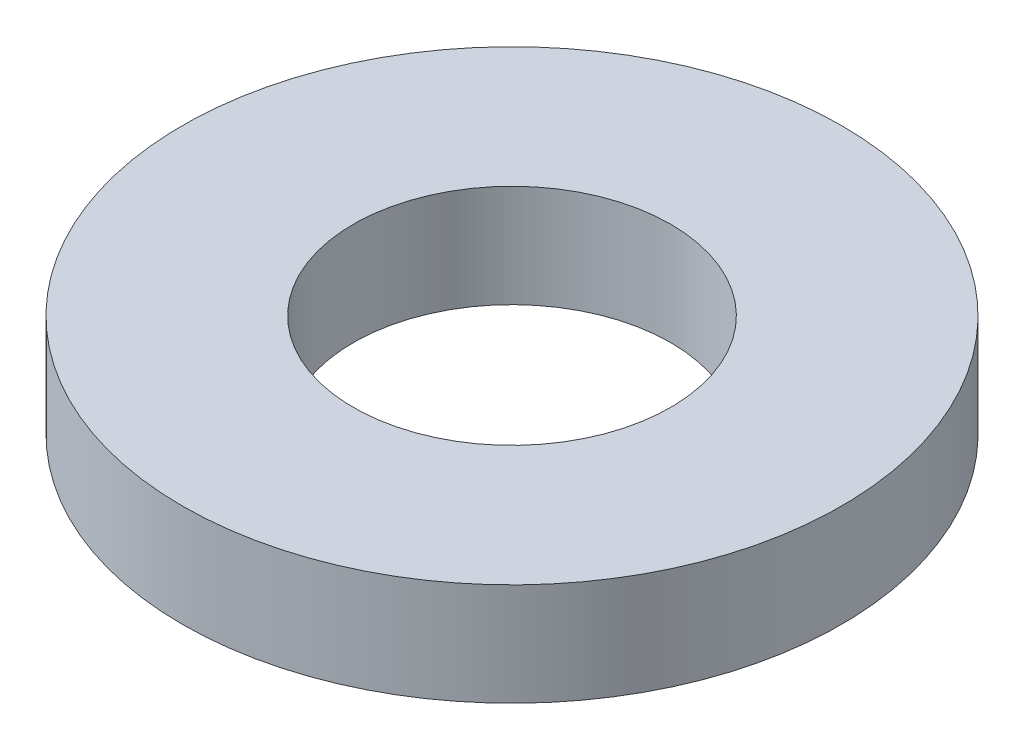
SolidWorks part; units mm, degrees
ref_plane "Front Plane" through (0, 0, 0) normal (0, 0, 1) x (1, 0, 0)
ref_plane "Top Plane" through (0, 0, 0) normal (0, 1, 0) x (1, 0, 0)
ref_plane "Right Plane" through (0, 0, 0) normal (1, 0, 0) x (0, 0, -1)
sketch "Sketch1" plane through (0, 0, 0) normal (0, 1, 0) x (1, 0, 0)
  circle A0 centre (0, 0) radius 67.5
  dimension "FLANGE_OD" = 135
extrude "Boss-Extrude1" add sketch "Sketch1" along normal blind 21
sketch "Sketch2" plane through (0, 0, 0) normal (0, 1, 0) x (1, 0, 0)
  circle A0 centre (0, 0) radius 32.5
  dimension "BORE_D" = 65
extrude "Cut-Extrude1" cut sketch "Sketch2" along normal through all
sketch "Sketch3" plane through (0, 21, 0) normal (0, 1, 0) x (1, 0, 0)
  circle A0 centre (0, 0) radius 26.7466 construction
  circle A1 centre (-26.7466, 0) radius 5.5032
  dimension "BOLT_D" = 11.0063
  dimension "BOLT_PCD" = 53.4932
extrude "Cut-Extrude2" cut sketch "Sketch3" against normal blind 17.4894 rebuild error yes
pattern_circular "CirPattern1" count 3 over 360 rebuild error yes
